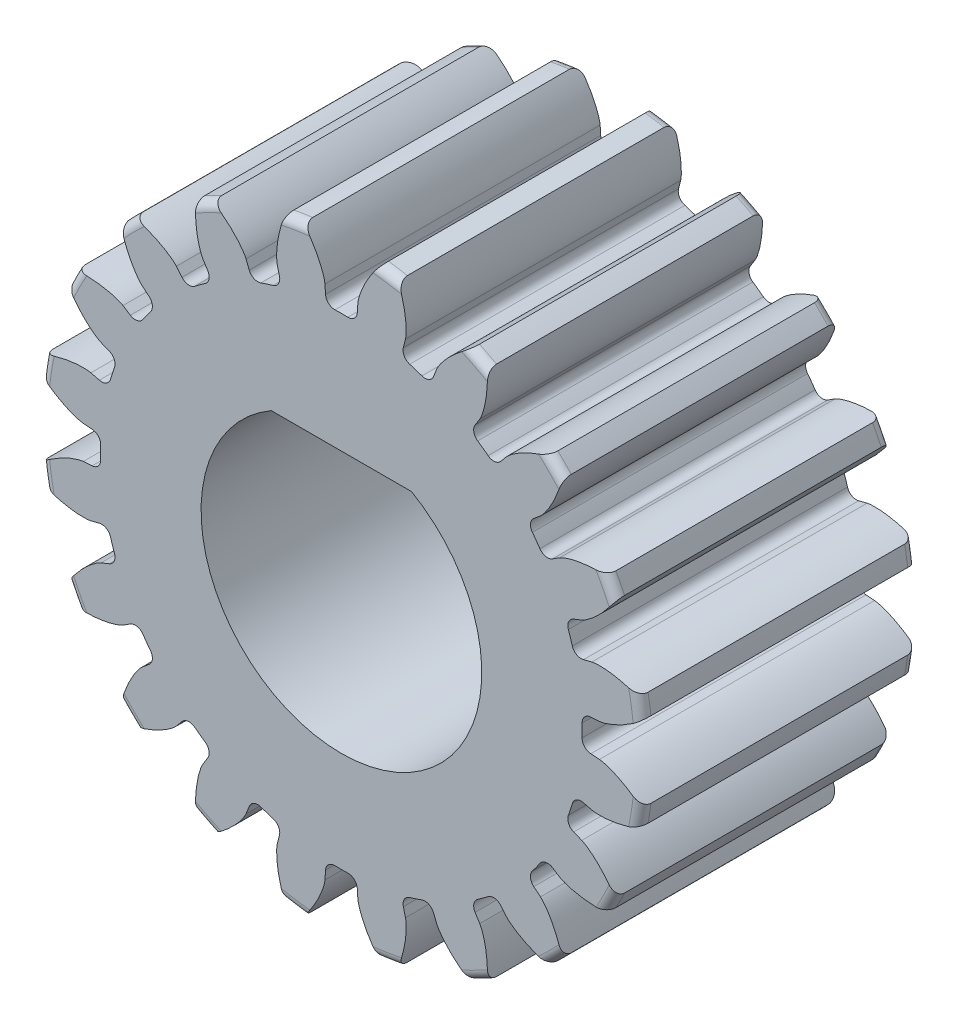
SolidWorks part; units mm, degrees
ref_plane "Front Plane" through (0, 0, 0) normal (0, 0, 1) x (1, 0, 0)
ref_plane "Top Plane" through (0, 0, 0) normal (0, 1, 0) x (1, 0, 0)
ref_plane "Right Plane" through (0, 0, 0) normal (1, 0, 0) x (0, 0, -1)
sketch "Sketch1" plane through (0, 0, 0) normal (0, 0, 1) x (1, 0, 0)
  line L0 (0, 0) -> (0, 12.7) construction
  line L1 (-4.0817, 14.1856) -> (4.0817, 11.2144) construction
  circle A0 centre (0, 0) radius 11.1125 construction
  circle A1 centre (0, 0) radius 13.97 construction
  circle A2 centre (0, 0) radius 12.7 construction
  circle A3 centre (0, 0) radius 11.9341 construction
  circle A4 centre (0, 0) radius 6.35 construction
  circle A5 centre (0, 0) radius 10.668 construction
  point P8 (254, 0)
  point P13 (254, 0)
  dimension "OD | Outside Diameter" = 27.94
  dimension "Root Diameter" = 22.225
  dimension "Gear Pitch Diameter" = 25.4
  dimension "Base Diameter" = 23.8682
  dimension "For Shaft Diameter" = 12.7
  dimension "Hub Diameter" = 21.336
  dimension "Pressure Angle" = 20
  dimension "Number of Teeth" = 508
  dimension "Gear Pitch | Diametral Pitch" = 508
sketch "Sketch2" plane through (0, 0, 0) normal (1, 0, 0) x (0, 0, -1)
  line L0 (-11.938, 0) -> (11.938, 0) construction
  line L1 (-11.938, 13.97) -> (11.938, 13.97) construction
  point P2 (0, 13.97)
  point P4 (-0.762, 0)
  point P6 (-0.762, 13.97)
  dimension "Overall Width" = 23.876
  dimension "Hub Width" = 11.176
  dimension "Face Width" = 12.7
sketch "Sketch3" plane through (0, 0, 0) normal (0, 0, 1) x (1, 0, 0)
  circle A0 centre (0, 0) radius 13.97
  circle A1 centre (0, 0) radius 13.97 construction
extrude "Boss-Extrude1" add sketch "Sketch3" against normal up to vertex (11.938 mm away) and the other way up to vertex (11.938 mm away) up to point (0, 0, -11.938) other way up to point (0, 0, 11.938)
sketch "Sketch5" plane through (0, 0, 0) normal (1, 0, 0) x (0, 0, -1)
  line L1 (-11.938, 13.97) -> (-0.762, 13.97)
  line L2 (-11.938, 13.97) -> (-11.938, 10.668)
  line L3 (-11.938, 10.668) -> (-0.762, 10.668)
  line L4 (-0.762, 13.97) -> (-0.762, 10.668)
  line L11 (11.938, 6.35) -> (-11.938, 6.35)
  line L12 (11.938, 6.35) -> (11.938, 0)
  line L13 (11.938, 0) -> (-11.938, 0)
  line L14 (-11.938, 6.35) -> (-11.938, 0)
  point P5 (0, 6.35)
  point P12 (0, 10.668)
revolve "Cut-Revolve1" cut sketch "Sketch5" angle 360 about L0
fillet "Fillet2" radius 0.4261 6 edges at (13.97, 0, -11.938) (6.35, 0, -11.938) (6.35, 0, 11.938) (10.668, 0, 0.762) (13.97, 0, 0.762) (10.668, 0, 11.938)
sketch "Sketch4" plane through (0, 0, 0) normal (0, 0, 1) x (1, 0, 0)
  line L0 (0, 0) -> (11.09, 0.7067) construction
  line L2 (0, 0) -> (11.09, -0.7067) construction
  line L4 (11.09, 0.7067) -> (11.9099, 0.7589)
  line L5 (11.9099, -0.7589) -> (11.09, -0.7067)
  arc A0 (11.09, 0.7067) -> (11.09, -0.7067) centre (0, 0) cw
  arc A3 (13.8601, 1.7486) -> (13.8601, -1.7486) centre (0, 0) cw
  circle A4 centre (0, 0) radius 13.97 construction
  spline S0 degree 4 poles (11.9099, 0.7589) (11.9132, 0.7592) (11.9223, 0.76) (11.9395, 0.7621) (11.9676, 0.7662) (12.0032, 0.7725) (12.049, 0.7819) (12.1028, 0.7946) (12.1617, 0.8101) (12.2255, 0.8288) (12.2889, 0.849) (12.3518, 0.8706) (12.4142, 0.8934) (12.4896, 0.9225) (12.5794, 0.9596) (12.6838, 1.0061) (12.8012, 1.0624) (12.9199, 1.1237) (13.0359, 1.1872) (13.152, 1.255) (13.2636, 1.3231) (13.3784, 1.3975) (13.4837, 1.4681) (13.6005, 1.5512) (13.6943, 1.6195) (13.8166, 1.7137) (13.8883, 1.7707) (13.9718, 1.8388) (14.0086, 1.8698) (14.0312, 1.8889) knots 0 0 0 0 0 0.005377 0.015084 0.028532 0.04661 0.064855 0.092111 0.119476 0.146842 0.174209 0.201575 0.228941 0.256307 0.307035 0.361767 0.4165 0.471232 0.525964 0.580697 0.635429 0.690161 0.744894 0.799626 0.854358 0.909091 0.954545 1 1 1 1 1 construction
  spline S1 degree 4 poles (11.9099, 0.7589) (11.9132, 0.7592) (11.9223, 0.76) (11.9395, 0.7621) (11.9676, 0.7662) (12.0032, 0.7725) (12.049, 0.7819) (12.1028, 0.7946) (12.1617, 0.8101) (12.2255, 0.8288) (12.2889, 0.849) (12.3518, 0.8706) (12.4142, 0.8934) (12.4896, 0.9225) (12.5794, 0.9596) (12.6838, 1.0061) (12.8012, 1.0624) (12.9199, 1.1237) (13.0359, 1.1872) (13.152, 1.255) (13.2636, 1.3231) (13.3784, 1.3975) (13.4837, 1.4681) (13.6005, 1.5512) (13.6943, 1.6195) (13.79, 1.6933) (13.8365, 1.7297) (13.8601, 1.7486) knots 0 0 0 0 0 0.005377 0.015084 0.028532 0.04661 0.064855 0.092111 0.119476 0.146842 0.174209 0.201575 0.228941 0.256307 0.307035 0.361767 0.4165 0.471232 0.525964 0.580697 0.635429 0.690161 0.744894 0.799626 0.854358 0.909091 0.909091 0.909091 0.909091 0.909091
  spline S2 degree 4 poles (11.9099, -0.7589) (11.9132, -0.7592) (11.9223, -0.76) (11.9395, -0.7621) (11.9676, -0.7662) (12.0032, -0.7725) (12.049, -0.7819) (12.1028, -0.7946) (12.1617, -0.8101) (12.2255, -0.8288) (12.2889, -0.849) (12.3518, -0.8706) (12.4142, -0.8934) (12.4896, -0.9225) (12.5794, -0.9596) (12.6838, -1.0061) (12.8012, -1.0624) (12.9199, -1.1237) (13.0359, -1.1872) (13.152, -1.255) (13.2636, -1.3231) (13.3784, -1.3975) (13.4837, -1.4681) (13.6005, -1.5512) (13.6943, -1.6195) (13.8166, -1.7137) (13.8883, -1.7707) (13.9718, -1.8388) (14.0086, -1.8698) (14.0312, -1.8889) knots 0 0 0 0 0 0.005377 0.015084 0.028532 0.04661 0.064855 0.092111 0.119476 0.146842 0.174209 0.201575 0.228941 0.256307 0.307035 0.361767 0.4165 0.471232 0.525964 0.580697 0.635429 0.690161 0.744894 0.799626 0.854358 0.909091 0.954545 1 1 1 1 1 construction
  spline S3 degree 4 poles (11.9099, -0.7589) (11.9132, -0.7592) (11.9223, -0.76) (11.9395, -0.7621) (11.9676, -0.7662) (12.0032, -0.7725) (12.049, -0.7819) (12.1028, -0.7946) (12.1617, -0.8101) (12.2255, -0.8288) (12.2889, -0.849) (12.3518, -0.8706) (12.4142, -0.8934) (12.4896, -0.9225) (12.5794, -0.9596) (12.6838, -1.0061) (12.8012, -1.0624) (12.9199, -1.1237) (13.0359, -1.1872) (13.152, -1.255) (13.2636, -1.3231) (13.3784, -1.3975) (13.4837, -1.4681) (13.6005, -1.5512) (13.6943, -1.6195) (13.79, -1.6933) (13.8365, -1.7297) (13.8601, -1.7486) knots 0 0 0 0 0 0.005377 0.015084 0.028532 0.04661 0.064855 0.092111 0.119476 0.146842 0.174209 0.201575 0.228941 0.256307 0.307035 0.361767 0.4165 0.471232 0.525964 0.580697 0.635429 0.690161 0.744894 0.799626 0.854358 0.909091 0.909091 0.909091 0.909091 0.909091
  dimension "D1" = 22.225
extrude "Cut-Extrude1" cut sketch "Sketch4" against normal through all both and the other way through all
fillet "Fillet1" radius 0.4261 2 edges at (11.09, -0.7067, -5.588) (11.09, 0.7067, -5.588)
pattern_circular "CirPattern1" count 20 over 360 about axis through (0, 0, 11.938) along (0, 0, -1) of "Cut-Extrude1", "Fillet1"
sketch "Sketch6" plane through (0, 0, 0.762) normal (0, 0, 1) x (1, 0, 0)
  circle A0 centre (-4.6855, 10.0976) radius 0.0377
sketch "Sketch7" plane through (0, 0, 11.938) normal (0, 0, 1) x (1, 0, 0)
  circle A0 centre (0, 0) radius 19.0024
extrude "Cut-Extrude3" cut sketch "Sketch7" against normal up to surface (11.176 mm away) up to face at (0, 0, 0.762)
sketch "Sketch8" plane through (0, 0, 0.762) normal (0, 0, 1) x (1, 0, 0)
  circle A0 centre (0, 0) radius 6.858
extrude "Boss-Extrude2" add sketch "Sketch8" against normal up to surface (12.7 mm away) up to face at (0, 0, -11.938)
sketch "Sketch9" plane through (0, 0, 0.762) normal (0, 0, 1) x (1, 0, 0)
  point P0 (0, 0)
sketch "Sketch10" plane through (0, 0, 0.762) normal (0, 0, 1) x (1, 0, 0)
  line L0 (-3.2385, 5.6092) -> (3.2385, 5.6092)
  arc A0 (-3.2385, 5.6092) -> (3.2385, 5.6092) centre (0, 0) ccw
  dimension "D1" = 12.954
  dimension "D2" = 6.477
extrude "Cut-Extrude4" cut sketch "Sketch10" against normal through all both and the other way through all
equation "\"Root Diameter@Sketch1\"=\"Root Diameter\""
equation "\"OD | Outside Diameter@Sketch1\"=\"Outside Diameter\""
equation "\"D1@CirPattern1\"=\"Number of Teeth\""
equation "\"Diametral Pitch\"=20"
equation "\"Number of Teeth\"= 20"
equation "\"Pressure Angle\"=20"
equation "\"Pitch Diameter\"= \"Number of Teeth\" / \"Diametral Pitch\""
equation "\"Base Diameter\"= \"Pitch Diameter\" * cos ( \"Pressure Angle\" )"
equation "\"Outside Diameter\"= ( \"Number of Teeth\" + 2 ) / \"Diametral Pitch\""
equation "\"Dedendum\"= 1.25 / \"Diametral Pitch\""
equation "\"Root Diameter\"= \"Pitch Diameter\" - ( 2 * \"Dedendum\" )"
equation "\"Pitch Angle\"= 360deg / \"Number of Teeth\""
equation "\"Alpha\"= sqr ( \"Pitch Diameter\" ^ 2 - \"Base Diameter\" ^ 2 ) / \"Base Diameter\" * 180 / PI - \"Pressure Angle\""
equation "\"Beta\"= ( \"Pitch Angle\" / 4 - \"Alpha\" )"
equation "\"Phi\"= sqr ( ( \"Outside Diameter\" / 2 ) ^ 2 - ( \"Base Diameter\" / 2 ) ^ 2 ) / ( \"Base Diameter\" / 2 )"
equation "\"Addendum\"= 1 / \"Diametral Pitch\""
equation "\"WorkingDepth\"= 2 / \"Diametral Pitch\""
equation "\"WholeDepth\"= 2.25 / \"Diametral Pitch\""
equation "\"Clearance\"= 0.25 / \"Diametral Pitch\""
equation "\"ToothThickness\"= ( pi * 2 ) / \"Diametral Pitch\""
equation "\"CircularPitch\"= pi / \"Diametral Pitch\""
equation "\"Number of Teeth@Sketch1\"=\"Number of Teeth\""
equation "\"Gear Pitch | Diametral Pitch@Sketch1\"=\"Diametral Pitch\""
equation "\"Pressure Angle@Sketch1\"=\"Pressure Angle\""
equation "\"Gear Pitch Diameter@Sketch1\"=\"Pitch Diameter\""
equation "\"Base Diameter@Sketch1\"=\"Base Diameter\""
equation "\"Fillet\"= \"Clearance\" * cos ( \"Pressure Angle\" ) * tan ( ( 90 + \"Pressure Angle\" ) / 2 )"
equation "\"D1@Fillet1\"=\"Fillet\""
equation "\"D1@Sketch4\"=if( \"Base Diameter\">\"Root Diameter\",\"Root Diameter\",\"Base Diameter\"-.00001)"
equation "\"D1@Fillet2\"=\"Fillet\""
